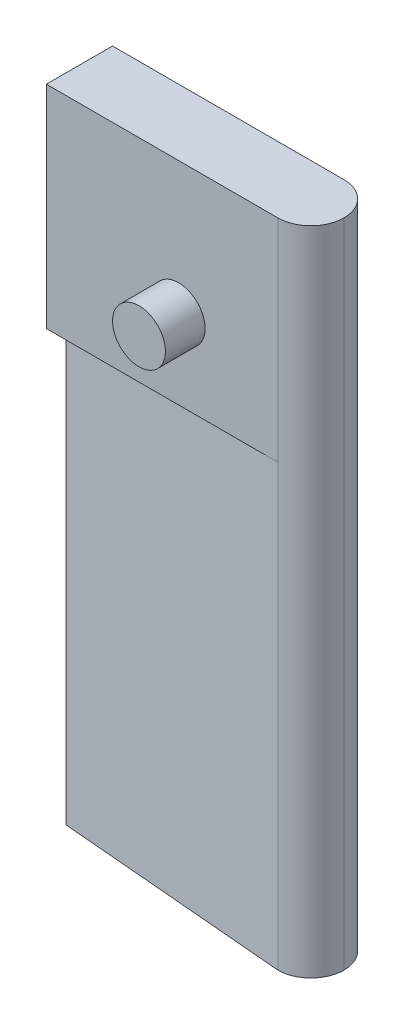
SolidWorks part; units mm, degrees
other "Markup1"
sketch "Sketch8"
ref_plane "Front Plane" through (0, 0, 0) normal (0, 0, 1) x (1, 0, 0)
ref_plane "Top Plane" through (0, 0, 0) normal (0, 1, 0) x (1, 0, 0)
ref_plane "Right Plane" through (0, 0, 0) normal (1, 0, 0) x (0, 0, -1)
sketch "Sketch1" plane through (0, 0, 0) normal (0, 0, 1) x (1, 0, 0)
  line L1 (-10, 0) -> (-10, 49.25)
  line L2 (10, 0) -> (10, 49.25)
  line L4 (-10, 49.25) -> (10, 49.25)
  line L5 (-10, 0) -> (10, 0)
  point P0 (0, 0)
  dimension "D2" = 20
  dimension "D7" = 20
  dimension "D9" = 49.25
extrude "Boss-Extrude1" add sketch "Sketch1" along normal mid plane 5
ref_plane "Plane1" through (0, 0, 0) normal (0, 0, 1) x (1, 0, 0)
sketch "Sketch13" plane through (0, 0, 2.5) normal (0, 0, 1) x (1, 0, 0)
  line L0 (10, 49.25) -> (-10, 49.25) construction
  point P0 (0, 39.25)
  point P3 (0, 49.25)
  dimension "D1" = 10
fillet "Fillet3" radius 2.5 2 edges at (10, 24.625, 2.5) (10, 24.625, -2.5)
sketch "Sketch11" plane through (0, 49.25, 0) normal (0, 1, 0) x (1, 0, 0)
  line L0 (7.5, 2.5) -> (-10, 1)
  line L1 (-10, -2.5) -> (-10, 2.5) construction
  line L2 (-10, 1) -> (-10, -1)
  line L3 (-10, -1) -> (7.5, -2.5)
  arc A0 (7.5, -2.5) -> (10, 0) centre (7.5, 0) ccw construction
  arc A1 (10, 0) -> (7.5, 2.5) centre (7.5, 0) ccw construction
  arc A2 (7.5, -2.5) -> (10, 0) centre (7.5, 0) ccw
  arc A3 (10, 0) -> (7.5, 2.5) centre (7.5, 0) ccw
  line M7 (-10, -2.5) -> (7.5, -2.5)
  line M11 (7.5, 2.5) -> (-10, 2.5)
  line M12 (-10, 2.5) -> (-10, -2.5)
  dimension "D1" = 2
extrude "Cut-Extrude1" cut sketch "Sketch11" against normal through all from offset 16 contours L0 M11 M12 | L3 M12 M7 offset against normal yes
sketch "Sketch14" plane through (0, 0, 0) normal (0, 0, 1) x (1, 0, 0)
  circle A0 centre (0, 39.25) radius 2
  dimension "D1" = 4
extrude "Boss-Extrude2" add sketch "Sketch14" along normal mid plane 11
